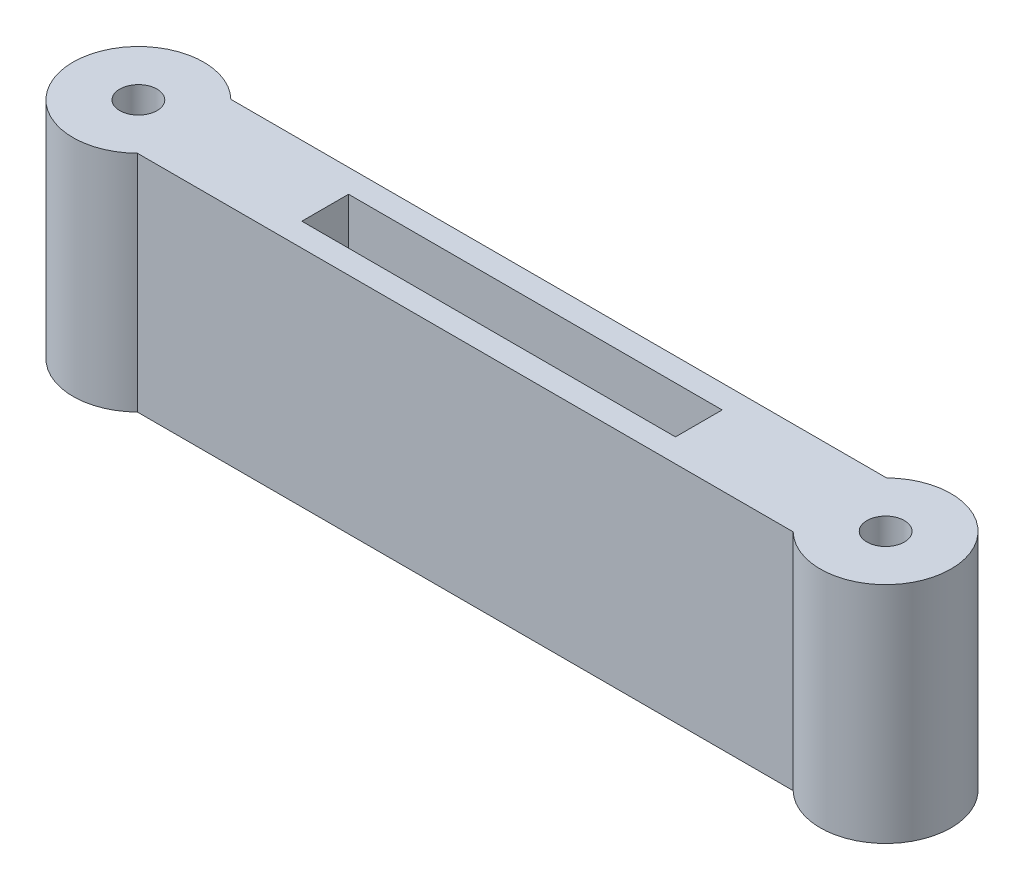
SolidWorks part; units mm, degrees
ref_plane "前视基准面" through (0, 0, 0) normal (0, 0, 1) x (1, 0, 0)
ref_plane "上视基准面" through (0, 0, 0) normal (0, 1, 0) x (1, 0, 0)
ref_plane "右视基准面" through (0, 0, 0) normal (1, 0, 0) x (0, 0, -1)
other "Configuration Table"
sketch "Sketch1" plane through (0, 0, 0) normal (0, 1, 0) x (1, 0, 0)
  line L1 (0, -25) -> (400, -25)
  line L2 (0, -25) -> (0, 25)
  line L3 (0, 25) -> (400, 25)
  line L4 (400, -25) -> (400, 25)
  line L5 (0, -25) -> (400, 25) construction
  line L6 (0, 25) -> (400, -25) construction
  point P0 (200, 0)
extrude "Boss-Extrude1" add sketch "Sketch1" along normal blind 60 and the other way blind 60
sketch "Sketch2" plane through (0, 0, 0) normal (0, 1, 0) x (1, 0, 0)
  line L0 (400, -25) -> (400, 25) construction
  circle A0 centre (0, 0) radius 35
  circle A1 centre (400, 0) radius 35
extrude "Boss-Extrude2" add sketch "Sketch2" along normal blind 60 and the other way blind 60
sketch "Sketch3" plane through (0, 0, 0) normal (0, 1, 0) x (1, 0, 0)
  circle A0 centre (0, 0) radius 10
  circle A1 centre (400, 0) radius 10
extrude "Cut-Extrude1" cut sketch "Sketch3" along normal blind 60 and the other way blind 60
sketch "Sketch4" plane through (0, 0, 0) normal (0, 1, 0) x (1, 0, 0)
  line L1 (100, -12.5) -> (300, -12.5)
  line L2 (100, -12.5) -> (100, 12.5)
  line L3 (100, 12.5) -> (300, 12.5)
  line L4 (300, -12.5) -> (300, 12.5)
  line L5 (100, -12.5) -> (300, 12.5) construction
  line L6 (100, 12.5) -> (300, -12.5) construction
  point P0 (200, 0)
extrude "Cut-Extrude2" cut sketch "Sketch4" along normal blind 60 and the other way blind 60
sketch3d "3DSketch1"
  line L0 (0, -30, 0) -> (0, 30, 0) construction
ref_axis "start_axis_y" through (0, -30, 0) along (0, 1, 0)
sketch3d "3DSketch2"
  line L0 (400, -30, 0) -> (400, 30, 0) construction
ref_axis "end_axis_y" through (400, -30, 0) along (0, 1, 0)
ref_plane "mid_plane_y" through (0, 0, 0) normal (0, 1, 0) x (1, 0, 0)
